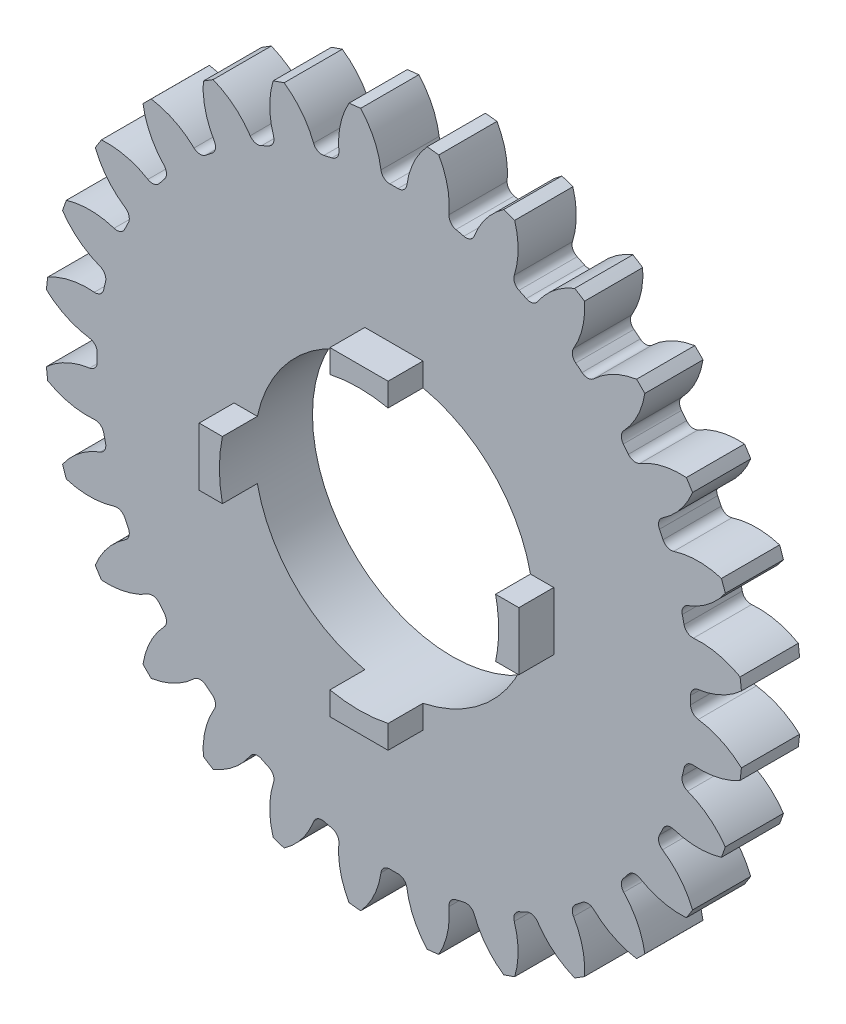
SolidWorks part; units mm, degrees
ref_plane "Front Plane" through (0, 0, 0) normal (0, 0, 1) x (1, 0, 0)
ref_plane "Top Plane" through (0, 0, 0) normal (0, 1, 0) x (1, 0, 0)
ref_plane "Right Plane" through (0, 0, 0) normal (1, 0, 0) x (0, 0, -1)
sketch "Sketch1" plane through (0, 0, 0) normal (0, 0, 1) x (1, 0, 0)
  line L4 (-1.0519, 25.4783) -> (0, 0) construction
  line L5 (0, 0) -> (0, 30) construction
  line L6 (0, 0) -> (3.3589, 29.8114) construction
  line L7 (-1.6208, 27.9531) -> (0.775, 28.9858) construction
  line L8 (-1.6208, 27.9531) -> (0.401, 28.0703) construction
  line L11 (1.6208, 27.9531) -> (-1.6208, 27.9531) construction
  circle A0 centre (0, 0) radius 25.5
  circle A1 centre (0, 0) radius 28 construction
  circle A2 centre (0, 0) radius 30
  arc A3 (-2.8616, 29.8632) -> (-1.0519, 25.4783) centre (-7.9602, 25.1931) cw
  arc A4 (2.8616, 29.8632) -> (1.0519, 25.4783) centre (7.9602, 25.1931) ccw
  point P5 (-28, 0)
  point P6 (-30, 0)
  point P7 (-25.5, 0)
  point P12 (-1.6208, 27.9531)
  point P22 (1.6208, 27.9531)
  dimension "D5" = 56
  dimension "D1" = 2.5
  dimension "D2" = 2
  dimension "D3" = 20
  dimension "D4" = 3.2416
  dimension "D6" = 6.429
  dimension "D7" = 0.5
extrude "Boss-Extrude1" add sketch "Sketch1" against normal blind 5 contours A2
extrude "Cut-Extrude1" cut sketch "Sketch1<4>" against normal blind 10 contours A4 A2 A3 A0 region at (0, 28.1291, 0)
sketch "Sketch1<4>" plane through (0, 0, 0) normal (0, 0, 1) x (1, 0, 0) same geometry as "Sketch1"
fillet "Fillet2" radius 0.76 2 edges at (1.0519, 25.4783, -2.5) (-1.0519, 25.4783, -2.5)
ref_axis "Axis1" through (0, 0, 0) along (0, 0, 1)
pattern_circular "CirPattern2" count 28 over 360 about axis through (0, 0, 0) along (0, 0, 1) of "Cut-Extrude1", "Fillet2"
sketch "Sketch2" plane through (0, 0, 0) normal (0, 0, 1) x (1, 0, 0)
  circle A0 centre (0, 0) radius 12
  dimension "D1" = 24
extrude "Cut-Extrude2" cut sketch "Sketch2" against normal up to surface (5 mm away) up to face at (0, 0, -5)
sketch "Sketch3" plane through (0, 0, 0) normal (0, 0, 1) x (1, 0, 0)
  line L0 (-2.5, 11.7367) -> (-2.5, 13.7367)
  line L1 (-2.5, 13.7367) -> (2.5, 13.7367)
  line L2 (2.5, 13.7367) -> (2.5, 11.7367)
  line L3 (0, 0) -> (0, 12) construction
  line L4 (13.7367, -2.5) -> (11.7367, -2.5)
  line L5 (13.7367, 2.5) -> (13.7367, -2.5)
  line L6 (11.7367, 2.5) -> (13.7367, 2.5)
  line L7 (-2.5, -13.7367) -> (-2.5, -11.7367)
  line L8 (2.5, -13.7367) -> (-2.5, -13.7367)
  line L9 (2.5, -11.7367) -> (2.5, -13.7367)
  line L10 (-13.7367, 2.5) -> (-11.7367, 2.5)
  line L11 (-13.7367, -2.5) -> (-13.7367, 2.5)
  line L12 (-11.7367, -2.5) -> (-13.7367, -2.5)
  circle A0 centre (0, 0) radius 12 construction
  arc A1 (-2.5, 11.7367) -> (2.5, 11.7367) centre (0, 0) cw
  arc A2 (11.7367, 2.5) -> (11.7367, -2.5) centre (0, 0) cw
  arc A3 (2.5, -11.7367) -> (-2.5, -11.7367) centre (0, 0) cw
  arc A4 (-11.7367, -2.5) -> (-11.7367, 2.5) centre (0, 0) cw
  point P24 (0, 0)
  dimension "D4" = 4
  dimension "D1" = 2.5
  dimension "D2" = 2.5
  dimension "D3" = 2
extrude "Boss-Extrude2" add sketch "Sketch3" along normal blind 3
equation "\"backlash\"= 0.1mm"
equation "\"module\"= 2mm"
equation "\"pressureAngle\"= 20deg"
equation "\"width\"= 10mm"
equation "\"D1@Sketch1\"= 1.25 * \"module\""
equation "\"D2@Sketch1\"=\"module\""
equation "\"D5@Sketch1\"=\"module\"*\"numberOfTeeth\""
equation "\"D1@Boss-Extrude1\"=\"width\"-5"
equation "\"D3@Sketch1\"=\"pressureAngle\""
equation "\"D1@Cut-Extrude1\"=\"width\""
equation "\"D1@CirPattern2\"=\"numberOfTeeth\""
equation "\"D1@Fillet2\"=0.38*\"module\""
equation "\"D4@Sketch1\"=pi*\"module\"/2+\"backlash\""
equation "\"numberOfTeeth\"= 28"
equation "\"D6@Sketch1\"=180/\"numberOfTeeth\""
equation "\"toothTipProfile\"= 1mm"
equation "\"D7@Sketch1\"=\"toothTipProfile\"/2"
equation "\"lengthOverallRack\"= pi * \"module\" * \"numberOfTeethRack\""
equation "\"numberOfTeethRack\"= 20"
